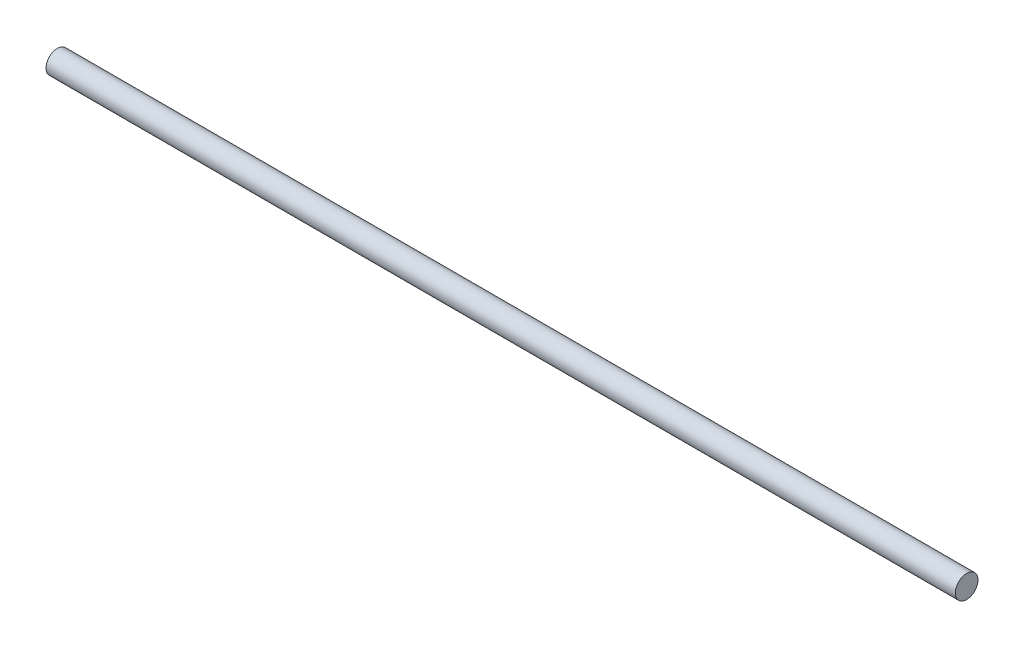
SolidWorks part; units mm, degrees
ref_plane "Front Plane" through (0, 0, 0) normal (0, 0, 1) x (1, 0, 0)
ref_plane "Top Plane" through (0, 0, 0) normal (0, 1, 0) x (1, 0, 0)
ref_plane "Right Plane" through (0, 0, 0) normal (1, 0, 0) x (0, 0, -1)
sketch "Sketch4" plane through (0, 0, 0) normal (1, 0, 0) x (0, 0, -1)
  circle A0 centre (57.6731, 144.1759) radius 3.81
  dimension "D1" = 7.62
extrude "Boss-Extrude2" add sketch "Sketch4" along normal blind 304.8 separate body
